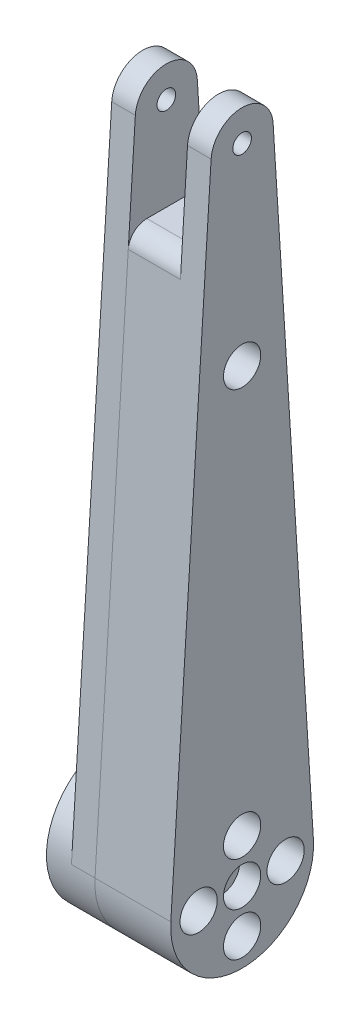
SolidWorks part; units mm, degrees
ref_plane "Front Plane" through (0, 0, 0) normal (0, 0, 1) x (1, 0, 0)
ref_plane "Top Plane" through (0, 0, 0) normal (0, 1, 0) x (1, 0, 0)
ref_plane "Right Plane" through (0, 0, 0) normal (1, 0, 0) x (0, 0, -1)
sketch "Sketch1" plane through (0, 0, 0) normal (1, 0, 0) x (0, 0, -1)
  line L0 (11.4773, 0.7222) -> (4.9901, 103.814)
  line L1 (-4.9901, 103.814) -> (-11.4773, 0.7222)
  circle A0 centre (0, 0) radius 11.5
  circle A1 centre (0, 103.5) radius 5
  circle A2 centre (0, 0) radius 10.25
  circle A3 centre (0, 103.5) radius 1.5
  circle A4 centre (0, 0) radius 1.6
  dimension "D1" = 10
  dimension "D2" = 23
  dimension "D4" = 20.5
  dimension "D5" = 3.2
  dimension "D6" = 3
  dimension "D3" = 103.5
extrude "Boss-Extrude1" add sketch "Sketch1" along normal blind 16 contours A1 | A1 L1 A0 L0 | A0 A2 | A2 region at (0, 49.1275, 0) region at (0, 0.3511, -11.1692) region at (0, 103.6526, -4.8562) region at (0, 0, 9.9601)
extrude "Boss-Extrude2" add sketch "Sketch1<4>" against normal blind 4 contours A0 A2 region at (0, 0.3511, -11.1692)
sketch "Sketch1<4>" plane through (0, 0, 0) normal (1, 0, 0) x (0, 0, -1) same geometry as "Sketch1"
extrude "Boss-Extrude3" add sketch "Sketch1<5>" against normal blind 2 contours A2 A4 region at (0, 0, 9.9601)
sketch "Sketch1<5>" plane through (0, 0, 0) normal (1, 0, 0) x (0, 0, -1) same geometry as "Sketch1"
hole_wizard "CBORE for M3 Hex Socket Head Cap Screw1" positions "Sketch2" profile "Sketch3" counterbore size "M3" standard "ISO" end condition through all
sketch "Sketch2" plane through (16, 0, 0) normal (1, 0, 0) x (0, 0, -1)
  point P0 (0, 7)
  dimension "D1" = 7
sketch "Sketch3" plane through (16, 7, 0) normal (0, 1, 0) x (0, 0, -1)
  line L0 (0, 0) -> (0, 20)
  line L1 (0, 20) -> (1.7, 20)
  line L3 (1.7, 20) -> (1.7, 12)
  line L4 (1.7, 12) -> (3, 12)
  line L5 (3, 12) -> (3, 0)
  line L7 (3, 0) -> (0, 0)
  line L11 (0, -6.35) -> (0, 107.95) construction
  dimension "Thru Hole Dia." = 3.4
  dimension "Thru Hole Depth" = 20
  dimension "C'Bore Dia." = 6
  dimension "C'Bore Depth" = 12
pattern_circular "CirPattern2" count 4 over 360 about axis through (-4, 0, 0) along (1, 0, 0) of "CBORE for M3 Hex Socket Head Cap Screw1"
sketch "Sketch4" plane through (16, 0, 0) normal (1, 0, 0) x (0, 0, -1)
  circle A0 centre (0, 0) radius 3
  circle A2 centre (0, 7) radius 3 construction
extrude "Cut-Extrude2" cut sketch "Sketch4" against normal blind 3.4
sketch "Sketch6" plane through (0, 0, 0) normal (0, 0, 1) x (1, 0, 0)
  line L1 (3.8, 108.5) -> (12.2, 108.5)
  line L2 (3.8, 108.5) -> (3.8, 88.5)
  line L3 (3.8, 88.5) -> (12.2, 88.5)
  line L4 (12.2, 108.5) -> (12.2, 88.5)
  line L5 (16, 108.5) -> (0, 108.5) construction
  point P8 (8, 108.5)
  dimension "D1" = 8.4
  dimension "D2" = 20
extrude "Cut-Extrude5" cut sketch "Sketch6" against normal through all both and the other way through all
fillet "Fillet1" radius 3 2 edges at (8, 88.5, -5.9538) (8, 88.5, 5.9538)
ref_plane "Plane1" through (3.8, 0, 0) normal (1, 0, 0) x (0, 0, -1)
split "Split1" trim tools "Plane1" bodies to split 111 resulting bodies 112 113
hole_wizard "CBORE for M3 Hex Socket Head Cap Screw2" positions "Sketch7" profile "Sketch8" counterbore size "M3" standard "ISO" end condition through all
sketch "Sketch7" plane through (16, 0, 0) normal (1, 0, 0) x (0, 0, -1)
  line L0 (3.1366, 88.5) -> (-3.1366, 88.5) construction
  point P0 (0, 72.5)
  point P5 (0, 0)
  dimension "D1" = 16
sketch "Sketch8" plane through (16, 72.5, 0) normal (0, 1, 0) x (0, 0, -1)
  line L0 (0, 0) -> (0, 20)
  line L1 (0, 20) -> (1.5, 20)
  line L3 (1.5, 20) -> (1.5, 8)
  line L4 (1.5, 8) -> (3, 8)
  line L5 (3, 8) -> (3, 0)
  line L7 (3, 0) -> (0, 0)
  line L11 (0, -6.35) -> (0, 107.95) construction
  dimension "Thru Hole Dia." = 3
  dimension "Thru Hole Depth" = 20
  dimension "C'Bore Dia." = 6
  dimension "C'Bore Depth" = 8
equation "\"D3@Sketch1\"=120-\"D2@Sketch1\"/2-\"D1@Sketch1\"/2"
